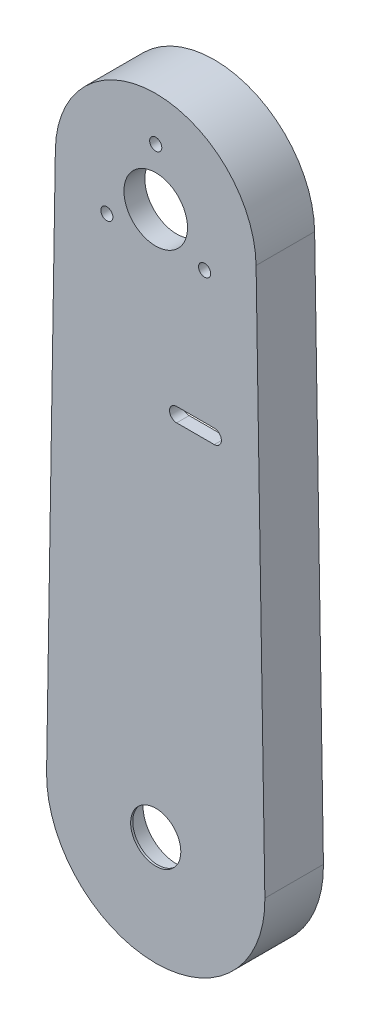
SolidWorks part; units mm, degrees
ref_plane "Front Plane" through (0, 0, 0) normal (0, 0, 1) x (1, 0, 0)
ref_plane "Top Plane" through (0, 0, 0) normal (0, 1, 0) x (1, 0, 0)
ref_plane "Right Plane" through (0, 0, 0) normal (1, 0, 0) x (0, 0, -1)
ref_plane "Plane1" through (0, 0, 344.5) normal (0, 0, 1) x (1, 0, 0)
sketch "Sketch1" plane through (0, 0, 344.5) normal (0, 0, 1) x (1, 0, 0)
  line L0 (276.0031, 300.3874) -> (273.9048, 170.4213)
  line L1 (326.0952, 170.4213) -> (323.9969, 300.3874)
  line L2 (305, 258.3) -> (314, 258.3)
  line L3 (314, 261.7) -> (305, 261.7)
  arc A0 (273.9048, 170.4213) -> (326.0952, 170.4213) centre (300, 170) ccw
  arc A1 (323.9969, 300.3874) -> (276.0031, 300.3874) centre (300, 300) ccw
  circle A2 centre (300, 170) radius 6
  arc A3 (314, 258.3) -> (314, 261.7) centre (314, 260) ccw
  arc A4 (305, 261.7) -> (305, 258.3) centre (305, 260) ccw
  circle A5 centre (300, 313.5) radius 1.45
  circle A6 centre (288.3087, 293.25) radius 1.45
  circle A7 centre (311.6913, 293.25) radius 1.45
extrude "Boss-Extrude1" add sketch "Sketch1" along normal blind 3
ref_plane "Plane2" through (0, 0, 342.5) normal (0, 0, 1) x (1, 0, 0)
sketch "Sketch2" plane through (0, 0, 342.5) normal (0, 0, 1) x (1, 0, 0)
  circle A0 centre (300, 300) radius 20
  circle A1 centre (300, 313.5) radius 1.45
  circle A2 centre (288.3087, 293.25) radius 1.45
  circle A3 centre (311.6913, 293.25) radius 1.45
extrude "Boss-Extrude2" add sketch "Sketch2" along normal blind 2
sketch "Sketch3" plane through (0, 0, 342.5) normal (0, 0, 1) x (1, 0, 0)
  circle A0 centre (300, 170) radius 12
  circle A1 centre (300, 170) radius 6
extrude "Boss-Extrude3" add sketch "Sketch3" along normal blind 2
ref_plane "Plane3" through (0, 0, 333.5) normal (0, 0, 1) x (1, 0, 0)
sketch "Sketch4" plane through (0, 0, 333.5) normal (0, 0, 1) x (1, 0, 0)
  line L0 (276.0031, 300.3874) -> (273.9048, 170.4213)
  line L1 (326.0952, 170.4213) -> (323.9969, 300.3874)
  line L2 (282.511, 300.619) -> (277.9152, 170.7817)
  line L3 (322.0848, 170.7817) -> (317.489, 300.619)
  arc A0 (273.9048, 170.4213) -> (326.0952, 170.4213) centre (300, 170) ccw
  arc A1 (323.9969, 300.3874) -> (276.0031, 300.3874) centre (300, 300) ccw
  arc A2 (277.9152, 170.7817) -> (322.0848, 170.7817) centre (300, 170) ccw
  arc A3 (317.489, 300.619) -> (282.511, 300.619) centre (300, 300) ccw
extrude "Boss-Extrude4" add sketch "Sketch4" along normal blind 11
sketch "Sketch5" plane through (0, 0, 333.5) normal (0, 0, 1) x (1, 0, 0)
  circle A0 centre (314.2894, 308.25) radius 5.05
extrude "Boss-Extrude5" add sketch "Sketch5" along normal blind 11
sketch "Sketch6" plane through (0, 0, 333.5) normal (0, 0, 1) x (1, 0, 0)
  circle A0 centre (285.7106, 308.25) radius 5.05
extrude "Boss-Extrude6" add sketch "Sketch6" along normal blind 11
sketch "Sketch7" plane through (0, 0, 333.5) normal (0, 0, 1) x (1, 0, 0)
  circle A0 centre (300, 240) radius 5.05
extrude "Boss-Extrude7" add sketch "Sketch7" along normal blind 11
sketch "Sketch8" plane through (0, 0, 333.5) normal (0, 0, 1) x (1, 0, 0)
  circle A0 centre (300, 200) radius 5.05
extrude "Boss-Extrude8" add sketch "Sketch8" along normal blind 11
sketch "Sketch9" plane through (0, 0, 333.5) normal (0, 0, 1) x (1, 0, 0)
  circle A0 centre (314.2894, 308.25) radius 2.05
  circle A1 centre (285.7106, 308.25) radius 2.05
  circle A2 centre (300, 240) radius 2.05
  circle A3 centre (300, 200) radius 2.05
extrude "Cut-Extrude1" cut sketch "Sketch9" along normal blind 6.7
sketch "Sketch10" plane through (0, 0, 342.5) normal (0, 0, 1) x (1, 0, 0)
  circle A0 centre (300, 300) radius 7.6
extrude "Cut-Extrude2" cut sketch "Sketch10" along normal blind 5
sketch "Sketch11" plane through (0, 0, 342.5) normal (0, 0, 1) x (1, 0, 0)
  circle A0 centre (300, 170) radius 8.05
extrude "Cut-Extrude3" cut sketch "Sketch11" along normal blind 4.5
ref_plane "Plane4" through (300, 0, 0) normal (1, 0, 0) x (0, 0, -1)
ref_plane "Plane5" through (0, 300, 0) normal (0, 1, 0) x (1, 0, 0)
ref_axis "HIP_AXIS" through (300, 300, 348.2) along (0, 0, -1)
ref_plane "Plane6" through (0, 170, 0) normal (0, 1, 0) x (1, 0, 0)
ref_axis "KNEE_AXIS" through (300, 170, 348.2) along (0, 0, -1)
